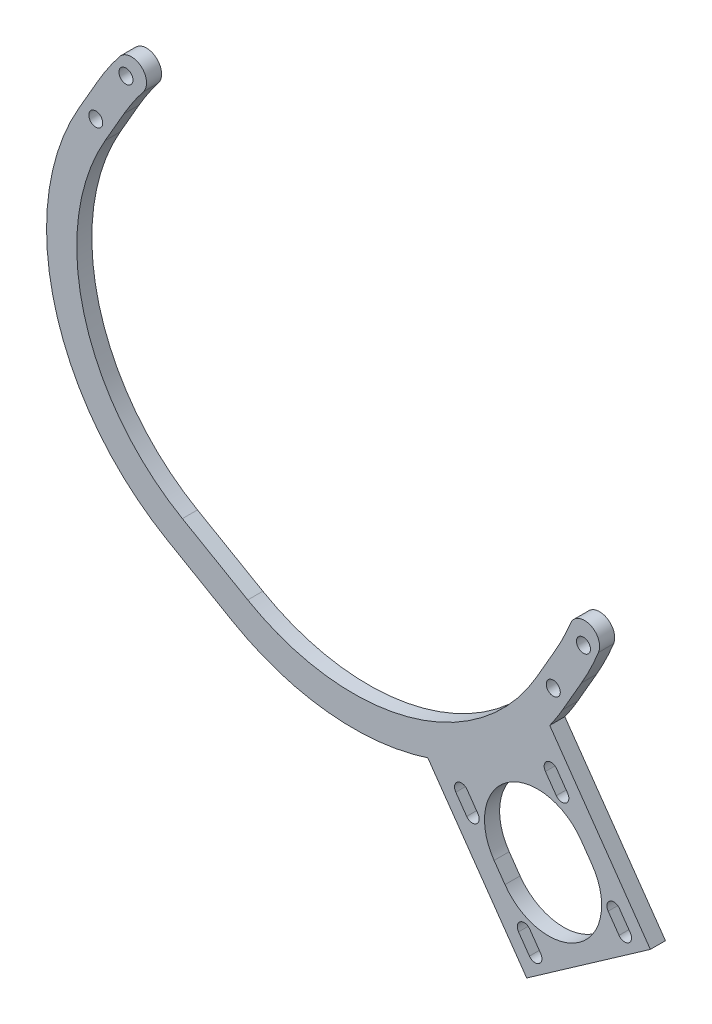
SolidWorks part; units mm, degrees
ref_plane "Front Plane" through (0, 0, 0) normal (0, 0, 1) x (1, 0, 0)
ref_plane "Top Plane" through (0, 0, 0) normal (0, 1, 0) x (1, 0, 0)
ref_plane "Right Plane" through (0, 0, 0) normal (1, 0, 0) x (0, 0, -1)
sketch "Sketch1" plane through (0, 0, -14.157) normal (0, 0, -1) x (-1, 0, 0)
  line L0 (-49.1723, -34.5021) -> (-53.1411, -27.628)
  line L1 (-2.2729, 1.7407) -> (29.3872, -53.0962) construction
  line L2 (20.2218, -53.0962) -> (27.0959, -49.1274)
  line L3 (33.9699, -45.1587) -> (20.2218, -53.0962) construction
  line L4 (17.0468, -47.5969) -> (23.9209, -43.6282)
  line L5 (-43.6731, -31.3271) -> (-47.6418, -24.453)
  line L6 (47.0648, 21.0604) -> (43.096, 27.9345)
  line L7 (30.7949, -39.6594) -> (23.9209, -43.6282)
  line L8 (33.9699, -45.1587) -> (27.0959, -49.1274)
  line L9 (52.564, 24.2354) -> (48.5953, 31.1095)
  arc A0 (-53.1411, -27.628) -> (-56.7299, -20.2712) centre (-2.2729, 1.7407) cw
  arc A3 (-61.0104, 1.7407) -> (-53.1411, -27.628) centre (-2.2729, 1.7407) ccw construction
  circle A4 centre (-53.5664, -20.5413) radius 1.1303 construction
  arc A5 (-49.1723, -34.5021) -> (20.2218, -53.0962) centre (-5.1782, -9.1021) ccw
  arc A6 (-43.6731, -31.3271) -> (17.0468, -47.5969) centre (-5.1782, -9.1021) ccw
  arc A7 (-47.6418, -24.453) -> (-50.8427, -17.8916) centre (-2.2729, 1.7407) cw
  arc A8 (-56.7299, -20.2712) -> (-50.8427, -17.8916) centre (-53.7863, -19.0814) cw
  arc A9 (44.0185, 37.8959) -> (39.014, 33.9872) centre (41.5163, 35.9416) ccw
  arc A10 (43.096, 27.9345) -> (39.014, 33.9872) centre (-2.2729, 1.7407) ccw
  arc A11 (47.0648, 21.0604) -> (30.7949, -39.6594) centre (8.5699, -1.1646) cw
  arc A12 (52.564, 24.2354) -> (33.9699, -45.1587) centre (8.5699, -1.1646) cw
  arc A13 (48.5953, 31.1095) -> (44.0185, 37.8959) centre (-2.2729, 1.7407) ccw
  dimension "D1" = 3.175
  dimension "D2" = 6.35
extrude "Boss-Extrude1" add sketch "Sketch1" along normal blind 3.175
ref_plane "Plane1" through (0, -58.42, 0) normal (0, 1, 0) x (-1, 0, 0)
ref_plane "Plane2" through (0, 0, -14.157) normal (0, 0, 1) x (1, 0, 0)
ref_axis "Axis2" through (-66.4483, 0, -14.157) along (1, 0, 0)
ref_axis "Axis3" through (0, 0, -25.4783) along (0, 0, 1)
ref_point "Point1"
ref_axis "Axis4" through (0, -70.9509, -14.157) along (0, 1, 0)
sketch "Sketch6" plane through (0, 0, -14.157) normal (0, 0, 1) x (1, 0, 0)
  line L0 (0, 0) -> (43.0544, -61.4881) construction
  line L1 (0, -70.9509) -> (0, 0.8498) construction
  line L10 (67.6372, -68.9187) -> (41.6291, -87.1298)
  line L15 (67.6372, -68.9187) -> (44.4797, -35.8464)
  line L16 (41.6291, -87.1298) -> (18.4716, -54.0574)
  line L17 (44.4797, -35.8464) -> (18.4716, -54.0574)
  line L18 (67.6372, -68.9187) -> (18.4716, -54.0574) construction
  line L19 (41.6291, -87.1298) -> (44.4797, -35.8464) construction
  line L20 (43.9251, -62.7315) -> (46.2124, -65.9981) construction
  line L21 (53.0799, -56.3212) -> (55.3672, -59.5878)
  line L22 (34.7702, -69.1418) -> (37.0575, -72.4084)
  line L23 (26.9048, -58.4844) -> (46.5539, -86.5463) construction
  line L24 (43.3867, -82.0231) -> (41.0994, -78.7565) construction
  line L25 (65.05, -72.8406) -> (45.0915, -44.3369) construction
  line L26 (42.2008, -82.8535) -> (39.9134, -79.5869)
  line L27 (44.5727, -81.1927) -> (42.2854, -77.9261)
  line L28 (27.9, -59.9058) -> (30.1874, -63.1725) construction
  line L29 (29.086, -59.0754) -> (31.3733, -62.342)
  line L30 (26.7141, -60.7363) -> (29.0014, -64.0029)
  line L31 (46.7507, -46.7065) -> (49.038, -49.9731) construction
  line L32 (47.9367, -45.876) -> (50.224, -49.1427)
  line L33 (45.5647, -47.5369) -> (47.852, -50.8035)
  line L34 (59.9501, -65.5571) -> (62.2374, -68.8237) construction
  line L35 (61.136, -64.7267) -> (63.4233, -67.9933)
  line L36 (58.7641, -66.3875) -> (61.0514, -69.6542)
  line L37 (30.1874, -63.1725) -> (49.038, -49.9731) construction
  arc A0 (42.2008, -82.8535) -> (44.5727, -81.1927) centre (43.3867, -82.0231) ccw
  arc A1 (42.2854, -77.9261) -> (39.9134, -79.5869) centre (41.0994, -78.7565) ccw
  arc A2 (-17.0468, -47.5969) -> (43.6731, -31.3271) centre (5.1782, -9.1021) ccw construction
  arc A3 (53.0799, -56.3212) -> (34.7702, -69.1418) centre (43.9251, -62.7315) ccw
  arc A4 (37.0575, -72.4084) -> (55.3672, -59.5878) centre (46.2124, -65.9981) ccw
  arc A5 (29.086, -59.0754) -> (26.7141, -60.7363) centre (27.9, -59.9058) ccw
  arc A6 (29.0014, -64.0029) -> (31.3733, -62.342) centre (30.1874, -63.1725) ccw
  arc A7 (47.9367, -45.876) -> (45.5647, -47.5369) centre (46.7507, -46.7065) ccw
  arc A8 (47.852, -50.8035) -> (50.224, -49.1427) centre (49.038, -49.9731) ccw
  arc A9 (61.136, -64.7267) -> (58.7641, -66.3875) centre (59.9501, -65.5571) ccw
  arc A10 (61.0514, -69.6542) -> (63.4233, -67.9933) centre (62.2374, -68.8237) ccw
  point P3 (45.0687, -64.3648)
  point P25 (42.2431, -80.3898)
  point P30 (29.0437, -61.5391)
  point P37 (47.8944, -48.3398)
  point P44 (61.0937, -67.1904)
  dimension "D4" = 11.176
  dimension "D5" = 11.5062
  dimension "D8" = 1.4478
  dimension "D9" = 23.0124
  dimension "D14" = 1.4478
  dimension "D15" = 1.4478
  dimension "D16" = 1.4478
  dimension "D19" = 3.9878
  dimension "D1" = 35
  dimension "D2" = 95.25
  dimension "D3" = 31.75
  dimension "D6" = 11.5062
  dimension "D7" = 3.9878
  dimension "D10" = 23.0124
  dimension "D11" = 3.9878
  dimension "D12" = 3.9878
  dimension "D13" = 3.9878
  dimension "D17" = 3.175
  dimension "D18" = 3.175
  dimension "D20" = 11.5062
extrude "Boss-Extrude2" add sketch "Sketch6" against normal up to surface (3.175 mm away) up to face at (-5.7343, -12.1282, -17.332)
hole_wizard "#4 Clearance Hole1" positions "Sketch5" profile "Sketch4" hole size "#4" standard "Ansi Inch" end condition through all
sketch "Sketch5" plane through (0, 0, -17.332) normal (0, 0, -1) x (-1, 0, 0)
  circle A1 centre (-53.5664, -20.5413) radius 1.1303 construction
  circle A2 centre (49.0206, 24.0227) radius 1.1303 construction
  point P0 (-53.5664, -20.5413)
  point P5 (-47.2164, -31.5398)
  point P8 (42.6706, 35.0212)
  point P11 (49.0206, 24.0227)
sketch "Sketch4" plane through (53.5664, -20.5413, -17.332) normal (1, 0, 0) x (0, 1, 0)
  line L0 (0, 0) -> (0, 3.175)
  line L1 (0, 3.175) -> (1.4732, 3.175)
  line L2 (1.4732, 3.175) -> (1.4732, 0)
  line L5 (1.4732, 0) -> (0, 0)
  line L11 (0, -6.35) -> (0, 107.95) construction
  dimension "Thru Hole Dia." = 2.9464
  dimension "Thru Hole Depth" = 3.175
